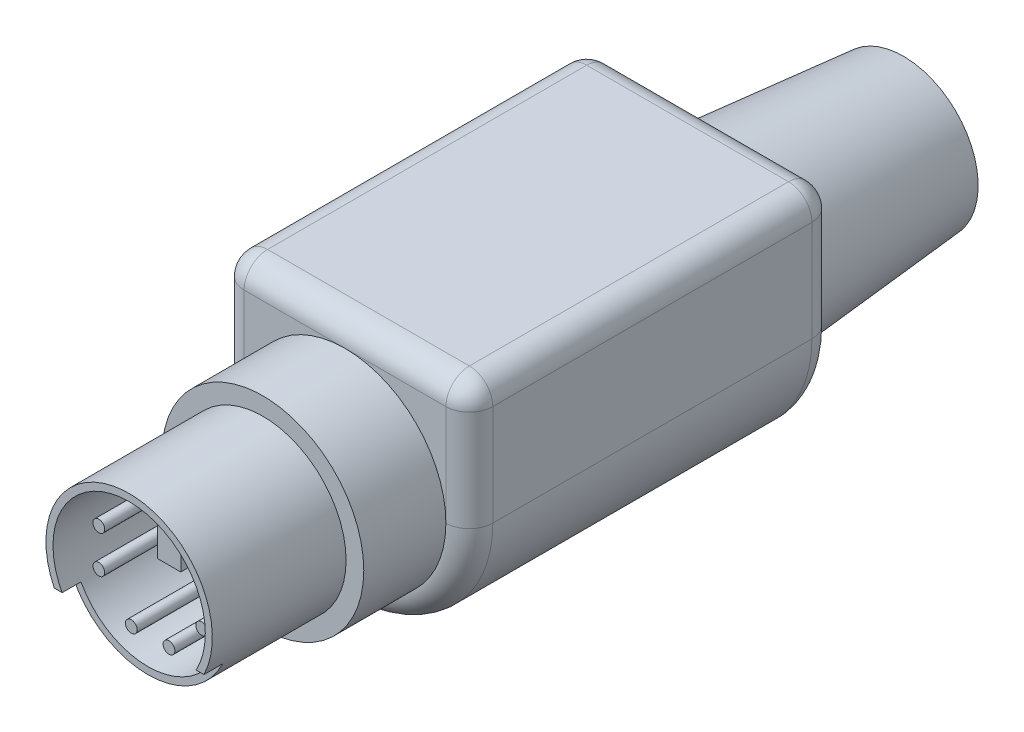
SolidWorks part; units mm, degrees
ref_plane "Plane1" through (0, 0, 0) normal (0, 0, 1) x (1, 0, 0)
ref_plane "Plane2" through (0, 0, 0) normal (0, 1, 0) x (1, 0, 0)
ref_plane "Plane3" through (0, 0, 0) normal (1, 0, 0) x (0, 0, -1)
sketch "Sketch1" plane through (0, 0, 0) normal (0, 0, 1) x (1, 0, 0)
  line L0 (0, 34.7472) -> (0, -38.5318) construction
  line L1 (6.731, 0) -> (6.731, 6.731)
  line L2 (-6.731, 0) -> (-6.731, 6.731)
  line L5 (-6.731, 6.731) -> (6.731, 6.731)
  arc A0 (-6.731, 0) -> (6.731, 0) centre (0, 0) ccw
  dimension "D1" = 13.462
extrude "Base-Extrude" add sketch "Sketch1" along normal blind 19.812
sketch "Sketch2" plane through (0, 0, 19.812) normal (0, 0, 1) x (1, 0, 0)
  circle A0 centre (0, 0) radius 5.461
  dimension "D1" = 10.922
extrude "Boss-Extrude1" add sketch "Sketch2" along normal blind 4.445
sketch "Sketch7" plane through (0, 0, 24.257) normal (0, 0, 1) x (1, 0, 0)
  circle A0 centre (0, 0) radius 4.503
extrude "Boss-Extrude3" add sketch "Sketch7" along normal blind 7.239
sketch "Sketch8" plane through (0, 0, 31.496) normal (0, 0, 1) x (1, 0, 0)
  circle A3 centre (0, 0) radius 4.122
  circle A4 centre (0, 0) radius 4.122
  dimension "D2" = 0.381
extrude "Cut-Extrude3" cut sketch "Sketch8" against normal up to surface (7.239 mm away) up to face at (5.461, 0, 24.257)
fillet "Fillet1" radius 1.27 10 edges at (0, 6.731, 19.812) (6.731, 3.3655, 19.812) (-6.731, 3.3655, 19.812) (0, -6.731, 19.812) (6.731, 6.731, 9.906) (-6.731, 6.731, 9.906) (0, 6.731, 0) (-6.731, 3.3655, 0) (0, -6.731, 0) (6.731, 3.3655, 0)
sketch "Sketch9" plane through (0, 0, 31.496) normal (0, 0, 1) x (1, 0, 0)
  line L0 (3.6246, -1.963) -> (4.0526, -1.963)
  line L1 (-4.0526, -1.963) -> (-3.6246, -1.963)
  circle A0 centre (0, 0) radius 4.122 construction
  circle A1 centre (0, 0) radius 4.503
  arc A2 (-4.0526, -1.963) -> (4.0526, -1.963) centre (0, 0) ccw
  arc A3 (-3.6246, -1.963) -> (3.6246, -1.963) centre (0, 0) ccw
  dimension "D1" = 0
extrude "Cut-Extrude4" cut sketch "Sketch9" against normal blind 1.016
sketch "Sketch10" plane through (0, 0, 24.257) normal (0, 0, 1) x (1, 0, 0)
  line L0 (-0.635, 2.598) -> (0.635, 2.598)
  line L1 (-0.635, 2.598) -> (-0.635, 0.058)
  line L2 (0.635, 0.058) -> (-0.635, 0.058)
  line L3 (0.635, 0.058) -> (0.635, 2.598)
  dimension "D1" = 1.27
  dimension "D2" = 2.54
  dimension "D3" = 0.635
extrude "Boss-Extrude4" add sketch "Sketch10" along normal blind 5.08
sketch "Sketch11" plane through (0, 0, 24.257) normal (0, 0, 1) x (1, 0, 0)
  circle A1 centre (1.0131, -2.7835) radius 0.3175
  circle A2 centre (-1.0263, -2.8198) radius 0.3175
  circle A3 centre (-2.7835, -1.0131) radius 0.3175
  circle A4 centre (2.7835, -1.0131) radius 0.3175
  circle A5 centre (2.7835, 1.0131) radius 0.3175
  circle A6 centre (-2.7835, 1.0131) radius 0.3175
  dimension "D1" = 0.635
extrude "Boss-Extrude5" add sketch "Sketch11" along normal blind 6.096
sketch "Sketch12" plane through (0, 0, 0) normal (0, 0, -1) x (-1, 0, 0)
  circle A0 centre (0, 0) radius 4.953
  dimension "D1" = 9.906
extrude "Boss-Extrude6" add sketch "Sketch12" along normal blind 10.414 draft 5
sketch "Sketch13" plane through (0, 0, -10.414) normal (0, 0, -1) x (-1, 0, 0)
  point P0 (0, 0)
other "CPoint1"
ref_axis "Axis1" through (0, 0, -20.414) along (0, 0, 1)
